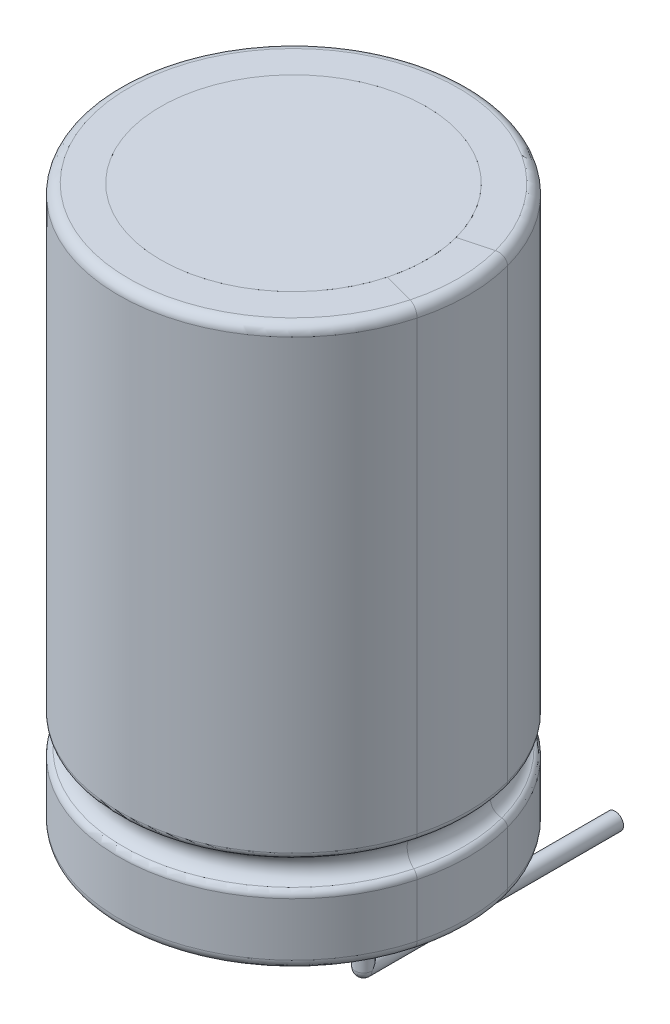
SolidWorks part; units mm, degrees
ref_plane "Alzado" through (0, 0, 0) normal (0, 0, 1) x (1, 0, 0)
ref_plane "Planta" through (0, 0, 0) normal (0, 1, 0) x (1, 0, 0)
ref_plane "Vista lateral" through (0, 0, 0) normal (1, 0, 0) x (0, 0, -1)
sketch "Croquis2" plane through (0, 0, 0) normal (0, 1, 0) x (1, 0, 0)
  line L1 (4.5881, 1.2294) -> (6.037, 1.6176)
  line L2 (4.5881, -1.2294) -> (6.037, -1.6176)
  circle A0 centre (0, 0) radius 6.25
  circle A1 centre (0, 0) radius 4.75
  dimension "D1" = 12.5
  dimension "D2" = 9.5
extrude "Saliente-Extruir2" add sketch "Croquis2" along normal blind 20 contours A1 L1 region at (0, 0, 0)
extrude "Saliente-Extruir3" add sketch "Croquis2<4>" along normal blind 20 separate body contours A1 L1 A0 L2 region at (-4.9253, 0, 0)
sketch "Croquis2<4>" plane through (0, 0, 0) normal (0, 1, 0) x (1, 0, 0) same geometry as "Croquis2"
extrude "Saliente-Extruir4" add sketch "Croquis2<5>" along normal blind 20 separate body contours A1 L2 A0 L1 region at (5.4711, 0, 0)
sketch "Croquis2<5>" plane through (0, 0, 0) normal (0, 1, 0) x (1, 0, 0) same geometry as "Croquis2"
fillet "Redondeo1" radius 0.35 1 edges at (-6.25, 20, 0)
fillet "Redondeo2" radius 0.35 2 edges at (6.25, 0, 0) (6.25, 20, 0)
fillet "Redondeo3" radius 0.35 1 edges at (-6.25, 0, 0)
sketch "Croquis3" plane through (0, 0, 0) normal (1, 0, 0) x (0, 0, -1)
  line L0 (0, -3.7684) -> (0, 22.1314)
  line L1 (-6.25, 19.65) -> (-6.25, 0.35) construction
  circle A0 centre (-6.25, 2.9605) radius 0.5
  dimension "D1" = 1
revolve "Cortar-Revolución1" cut sketch "Croquis3" angle 360 about L0
fillet "Redondeo4" radius 0.25 2 edges at (6.25, 2.4605, 0) (6.25, 3.4605, 0)
fillet "Redondeo5" radius 0.25 2 edges at (-6.25, 2.4605, 0) (-6.25, 3.4605, 0)
sketch "Croquis4" plane through (0, 0, 0) normal (0, 1, 0) x (1, 0, 0)
  circle A0 centre (0, 0) radius 2.5041 construction
  circle A3 centre (-2.5041, 0) radius 0.3
  circle A4 centre (2.5041, 0) radius 0.3
extrude "Saliente-Extruir7" add sketch "Croquis4" against normal blind 3 separate body
sketch "Croquis7" plane through (0, 0, 0) normal (0, 0, 1) x (1, 0, 0)
  line L0 (-2.8041, -3) -> (-2.2041, -3) construction
  line L1 (2.2041, -3) -> (2.8041, -3) construction
  circle A0 centre (-2.5041, -3) radius 0.3
  circle A1 centre (2.5041, -3) radius 0.3
extrude "Saliente-Extruir9" add sketch "Croquis7" against normal blind 9
sketch "Croquis8" plane through (0, 0, 0) normal (0, 0, 1) x (1, 0, 0)
  line L1 (2.8041, -3) -> (2.2041, -3)
  line L2 (2.8041, -3) -> (2.2041, -3)
  line L3 (-2.2041, -3) -> (-2.8041, -3)
  line L4 (-2.2041, -3) -> (-2.8041, -3)
  arc A1 (2.2041, -3) -> (2.8041, -3) centre (2.5041, -3) ccw
  arc A2 (2.2041, -3) -> (2.8041, -3) centre (2.5041, -3) ccw
  arc A3 (-2.8041, -3) -> (-2.2041, -3) centre (-2.5041, -3) ccw
  arc A4 (-2.8041, -3) -> (-2.2041, -3) centre (-2.5041, -3) ccw
  dimension "D1" = 0
  dimension "D2" = 0
revolve "Revolución5" add sketch "Croquis8" angle 360 about L2
revolve "Revolución6" add sketch "Croquis8<3>" angle 360 about L2
sketch "Croquis8<3>" plane through (0, 0, 0) normal (0, 0, 1) x (1, 0, 0) same geometry as "Croquis8"
